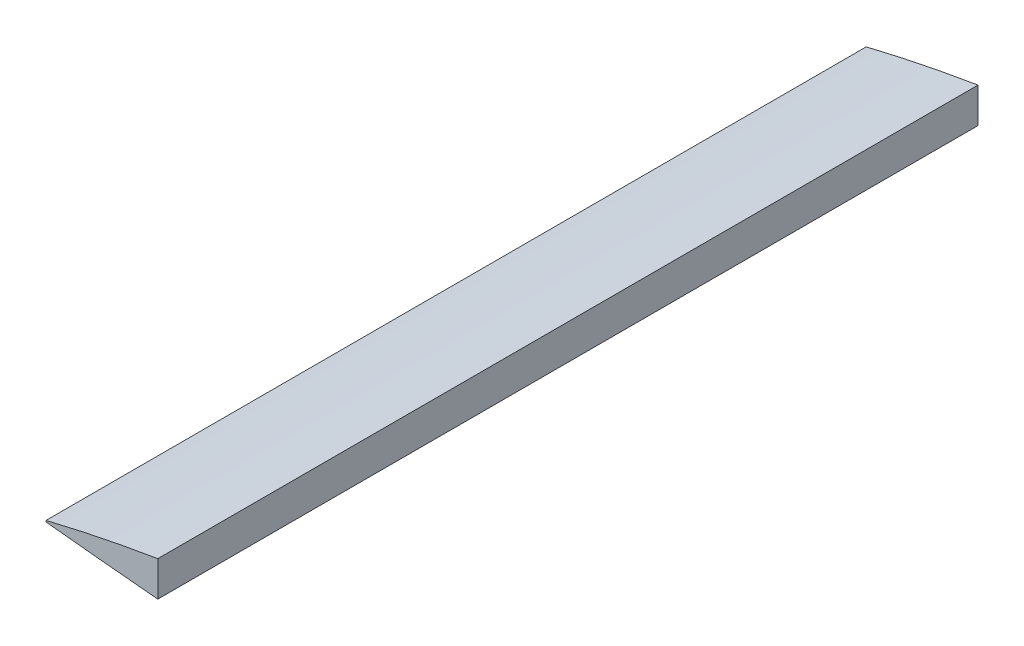
SolidWorks part; units mm, degrees
ref_plane "Front Plane" through (0, 0, 0) normal (0, 0, 1) x (1, 0, 0)
ref_plane "Top Plane" through (0, 0, 0) normal (0, 1, 0) x (1, 0, 0)
ref_plane "Right Plane" through (0, 0, 0) normal (1, 0, 0) x (0, 0, -1)
sketch "Sketch1" plane through (0, 0, 0) normal (0, 0, 1) x (1, 0, 0)
  line L0 (-237.3661, 17.5023) -> (-237.3661, -8.6743)
  line L1 (-320.765, 0.5123) -> (-320.765, -0.5041)
  spline S0 degree 3 poles (-237.3661, 17.5023) (-239.8019, 17.0983) (-245.7286, 16.1153) (-254.935, 14.4753) (-264.7764, 12.6474) (-273.9672, 10.8586) (-282.4535, 9.1393) (-290.1848, 7.5144) (-297.1155, 6.0094) (-303.2051, 4.6483) (-308.4182, 3.4537) (-312.7248, 2.4459) (-316.1, 1.6425) (-318.5247, 1.0579) (-319.9739, 0.7056) (-320.6133, 0.5494) (-320.765, 0.5123) knots 0 0 0 0 0.087007 0.211705 0.329527 0.439741 0.541661 0.634652 0.718135 0.791585 0.85454 0.906603 0.947445 0.976805 0.994497 1 1 1 1
  spline S1 degree 3 poles (-237.3661, -8.6743) (-239.4751, -8.4831) (-245.0808, -7.9749) (-253.9919, -7.1469) (-263.889, -6.2146) (-273.1542, -5.3269) (-281.7285, -4.4926) (-289.557, -3.719) (-296.5894, -3.0139) (-302.7801, -2.3837) (-308.0889, -1.8378) (-312.4807, -1.376) (-315.9277, -1.0227) (-318.4047, -0.7374) (-319.9003, -0.617) (-320.5749, -0.5034) (-320.7538, -0.504) (-320.765, -0.5041) knots 0 0 0 0 0.075811 0.201508 0.320388 0.431695 0.534719 0.628797 0.713321 0.78774 0.851567 0.90438 0.945827 0.975633 0.993597 0.999599 1 1 1 1
extrude "Boss-Extrude1" add sketch "Sketch1" along normal blind 612
ref_plane "Plane1" through (0, 0, 83.9) normal (0, 0, 1) x (1, 0, 0)
sketch "Sketch2" plane through (0, 0, 83.9) normal (0, 0, 1) x (1, 0, 0)
  line L0 (-261.074, -9.053) -> (-240.074, -9.053)
  line L1 (-240.074, -9.053) -> (-240.074, 2.447)
  line L2 (-240.074, 2.447) -> (-261.074, 2.447)
  line L3 (-261.074, 2.447) -> (-261.074, -9.053)
extrude "Cut-Extrude1" cut sketch "Sketch2" along normal blind 13
